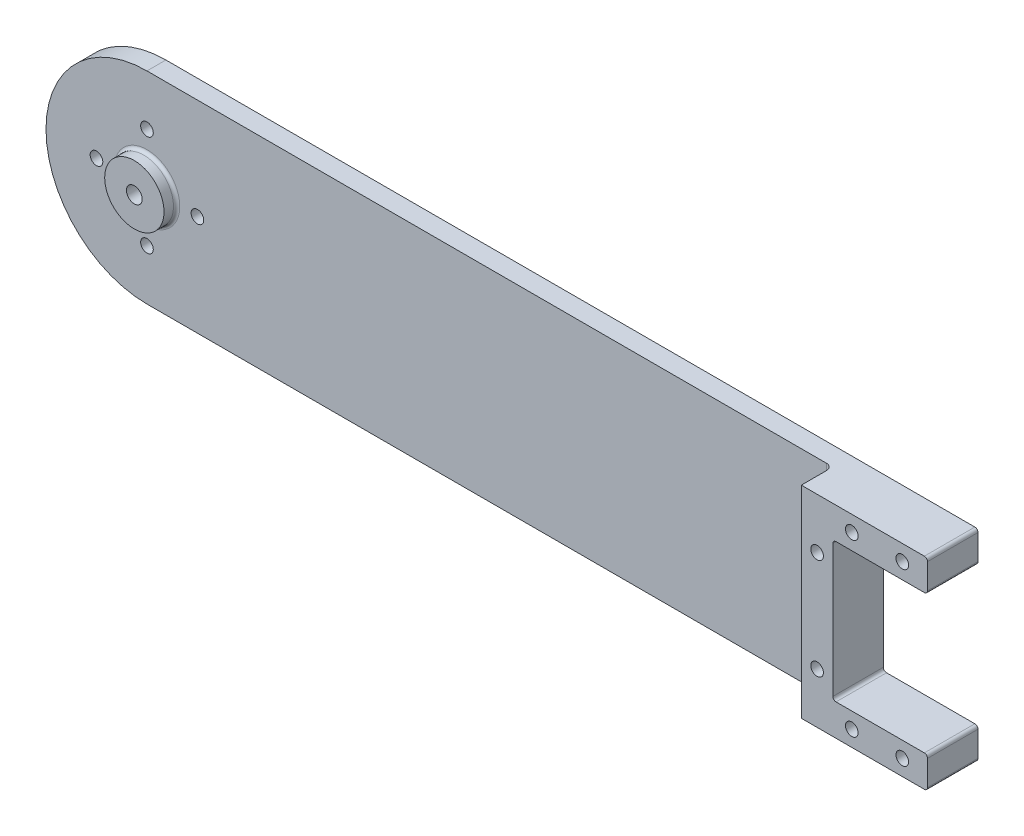
SolidWorks part; units mm, degrees
material "ABS"
ref_plane "Ön Düzlem" through (0, 0, 0) normal (0, 0, 1) x (1, 0, 0)
ref_plane "Üst Düzlem" through (0, 0, 0) normal (0, 1, 0) x (1, 0, 0)
ref_plane "Sağ Düzlem" through (0, 0, 0) normal (1, 0, 0) x (0, 0, -1)
sketch "Çizim1" plane through (0, 0, 0) normal (0, 0, 1) x (1, 0, 0)
  line L0 (-61, -16) -> (59, -16)
  line L1 (-61, 16) -> (59, 16)
  line L3 (59, 16) -> (75, 16)
  line L4 (59, 16) -> (59, -16)
  line L5 (59, -16) -> (75, -16)
  line L6 (75, 16) -> (75, -16)
  arc A0 (59, 16) -> (75, 0) centre (59, 0) cw
  arc A1 (-61, 16) -> (-77, 0) centre (-61, 0) ccw
  circle A2 centre (-61, 0) radius 16
  circle A3 centre (59, 0) radius 16
  point P0 (0, 0)
  dimension "D3" = 16
  dimension "D4" = 32
  dimension "D5" = 32
  dimension "D7" = 16
  dimension "D8" = 61
  dimension "D2" = 120
  dimension "D6" = 120
  dimension "D9" = 16
  dimension "D10" = 32
  dimension "D11" = 16
  dimension "D12" = 152
extrude "Yükseklik-Ekstrüzyon1" add sketch "Çizim1" along normal blind 3 contours A3 L1 A2 L0 | A0 A3 | A3 | L4 L3 L6 L5 | A2 region at (-1, 0, 0) region at (65.7906, 0, 0)
sketch "Çizim2" plane through (0, 0, 3) normal (0, 0, 1) x (1, 0, 0)
  circle A0 centre (-61, 0) radius 8 construction
  circle A1 centre (-61, 0) radius 4
  point P4 (-61, 8)
  point P5 (-53, 0)
  point P6 (-61, -8)
  point P7 (-69, 0)
  dimension "D1" = 16
  dimension "D2" = 8
extrude "Kes-Ekstrüzyon1" cut sketch "Çizim2" against normal blind 0.6
sketch "Çizim3" plane through (0, 0, 2.4) normal (0, 0, 1) x (1, 0, 0)
  circle A0 centre (-61, 0) radius 2.15
  dimension "D1" = 4.3
extrude "Kes-Ekstrüzyon3" cut sketch "Çizim3" against normal through all
hole_wizard "M2 Düz Başlı Makine Vidası İçin Havşa1" positions "3B Çizim1" profile "Çizim7" countersink size "M2" standard "ANSI Metrik" end condition through all
sketch3d "3B Çizim1"
  point P0 (-61, 8, 3)
  point P3 (-53, 0, 3)
  point P6 (-61, -8, 3)
  point P9 (-69, 0, 3)
sketch "Çizim7" plane through (-61, 8, 3) normal (1, 0, 0) x (0, -1, 0)
  line L0 (0, 0) -> (0, 6)
  line L1 (0, 6) -> (1, 6)
  line L2 (1, 6) -> (1, 0.3)
  line L3 (1, 0.3) -> (1.3, 0)
  line L5 (1.3, 0) -> (0, 0)
  line L6 (-1, 0.3) -> (-1.3, 0) construction
  line L11 (0, -6.35) -> (0, 107.95) construction
  dimension "Thru Hole Dia." = 2
  dimension "Thru Hole Depth" = 6
  dimension "Near C'Sink Dia." = 2.6
  dimension "Near C'Sink Angle" = 90
thread "Diş2" pitch 0.4 method cut profile "Diş Profili3" start angle 0, offset 0, length 5, pitch 0.4, diameter 2
ref_plane "Düzlem3" through (-62, 8, 2.7) normal (0, -1, 0) x (-1, 0, 0)
sketch "Diş Profili3" plane through (-62, 8, 2.7) normal (0, -1, 0) x (-1, 0, 0)
  line L0 (0, 0) -> (0, 0.4) construction
  line L1 (0, 0) -> (0.2165, 0.125)
  line L2 (0.2165, 0.125) -> (0.2165, 0.175)
  line L3 (0.2165, 0.175) -> (0, 0.3)
  line L4 (0.2165, 0.15) -> (0, 0.15) construction
  line L11 (0, 0) -> (0, 0.3)
  point P2 (0, 0)
  dimension "Pitch" = 0.4
  dimension "Profile_Angle" = 60
  dimension "Profile_Land" = 0.05
  dimension "Profile_Height" = 0.2165
pattern_circular "Dairesel Kaplama1" count 4 over 360 about axis through (-61, 0, 3) along (0, 0, 1) of "Diş2"
sketch "Çizim26" plane through (0, 0, 3) normal (0, 0, 1) x (1, 0, 0)
  line L0 (75, 16) -> (75, -16) construction
  line L1 (75, 11) -> (52.7, 11)
  line L2 (75, 11) -> (75, -11)
  line L3 (75, -11) -> (52.7, -11)
  line L4 (52.7, 11) -> (52.7, -11)
  line L5 (-61, -16) -> (75, -16) construction
  line L6 (-61, 16) -> (75, 16) construction
  point P8 (71.7, 13.5)
  point P9 (63.7, 13.5)
  point P10 (55.7, 13.5)
  point P11 (50.2, 8)
  point P12 (50.2, -8)
  point P13 (55.7, -13.5)
  point P14 (63.7, -13.5)
  point P15 (71.7, -13.5)
  dimension "D1" = 22.3
  dimension "D2" = 22
  dimension "D3" = 5
  dimension "D4" = 8
  dimension "D5" = 8
  dimension "D6" = 8
  dimension "D7" = 8
  dimension "D8" = 2.5
  dimension "D9" = 2.5
  dimension "D10" = 3.3
  dimension "D11" = 3.3
  dimension "D12" = 8
  dimension "D13" = 2.5
  dimension "D14" = 2.5
  dimension "D15" = 8
extrude "Kes-Ekstrüzyon4" cut sketch "Çizim26" against normal through all
sketch "Vida Del. Ref" plane through (0, 0, 0) normal (0, 0, -1) x (-1, 0, 0)
  point P0 (-71.7, 13.5)
  point P1 (-63.7, 13.5)
  point P3 (-55.7, 13.5)
  point P5 (-50.2, 8)
  point P7 (-50.2, -8)
  point P9 (-55.7, -13.5)
  point P11 (-63.7, -13.5)
  point P13 (-71.7, -13.5)
hole_wizard "M2 Düz Başlı Makine Vidası İçin Havşa2" positions "3B Çizim4" profile "Çizim32" countersink size "M2" standard "ANSI Metrik" end condition through all
sketch3d "3B Çizim4"
  point P0 (71.7, 13.5, 0)
  point P3 (63.7, 13.5, 0)
  point P6 (55.7, 13.5, 0)
  point P9 (50.2, 8, 0)
  point P12 (50.2, -8, 0)
  point P15 (55.7, -13.5, 0)
  point P18 (63.7, -13.5, 0)
  point P21 (71.7, -13.5, 0)
sketch "Çizim32" plane through (71.7, 13.5, 0) normal (1, 0, 0) x (0, 1, 0)
  line L0 (0, 0) -> (0, 3)
  line L1 (0, 3) -> (1.1, 3)
  line L2 (1.1, 3) -> (1.1, 0.2)
  line L3 (1.1, 0.2) -> (1.3, 0)
  line L5 (1.3, 0) -> (0, 0)
  line L6 (-1.1, 0.2) -> (-1.3, 0) construction
  line L11 (0, -6.35) -> (0, 107.95) construction
  dimension "Thru Hole Dia." = 2.2
  dimension "Thru Hole Depth" = 3
  dimension "Near C'Sink Dia." = 2.6
  dimension "Near C'Sink Angle" = 90
mirror "Sol Link Başlangıç" about plane through (0, 0, 0) normal (0, 0, 1) of "Kes-Ekstrüzyon4", "Kes-Ekstrüzyon3", "Kes-Ekstrüzyon1", "Yükseklik-Ekstrüzyon1", "M2 Düz Başlı Makine Vidası İçin Havşa1"
sketch "Çizim35" plane through (0, 16, 0) normal (0, 1, 0) x (1, 0, 0)
  line L0 (75, -3) -> (75, 3) construction
  line L1 (-77, -3) -> (75, -3)
  line L2 (-77, -3) -> (-77, 0)
  line L3 (-77, 0) -> (75, 0)
  line L4 (75, -3) -> (75, 0)
extrude "Kes-Ekstrüzyon5" cut sketch "Çizim35" against normal through all
sketch "Çizim37" plane through (0, 0, 0) normal (0, 0, 1) x (1, 0, 0)
  circle A0 centre (-61, 0) radius 3.75
  circle A1 centre (-61, 0) radius 2.15
  dimension "D1" = 4.3
  dimension "D2" = 7.5
extrude "Yükseklik-Ekstrüzyon2" add sketch "Çizim37" along normal blind 2
sketch "Çizim38" plane through (0, 0, -3) normal (0, 0, -1) x (-1, 0, 0)
  line L0 (61, -16) -> (-75, -16) construction
  line L1 (-75, 16) -> (-47.7, 16)
  line L2 (-75, 16) -> (-75, -16)
  line L3 (-75, -16) -> (-47.7, -16)
  line L4 (-47.7, 16) -> (-47.7, -16)
  line L6 (-75, 11) -> (-52.7, 11)
  line L7 (-75, 11) -> (-75, -11)
  line L8 (-75, -11) -> (-52.7, -11)
  line L9 (-52.7, 11) -> (-52.7, -11)
  line M8 (-75, 16) -> (-75, 11)
  line M9 (-75, 11) -> (-52.7, 11)
  line M10 (-52.7, 11) -> (-52.7, -11)
  line M11 (-52.7, -11) -> (-75, -11)
  line M12 (-75, -11) -> (-75, -16)
  line M13 (-75, -16) -> (61, -16)
  line M15 (61, 16) -> (-75, 16)
  dimension "D1" = 5
extrude "Yükseklik-Ekstrüzyon3" add sketch "Çizim38" against normal blind 8 contours L4 M15 M8 M9 M10 M11 M12 M13 region at (61.35, 15.5794, -3)
sketch "Vida Del. Ref_v2" plane through (0, 0, -3) normal (0, 0, -1) x (-1, 0, 0)
  point P0 (-71.7, 13.5)
  point P1 (-63.7, 13.5)
  point P3 (-55.7, 13.5)
  point P5 (-50.2, 8)
  point P7 (-50.2, -8)
  point P9 (-55.7, -13.5)
  point P11 (-63.7, -13.5)
  point P13 (-71.7, -13.5)
hole_wizard "M2 Düz Başlı Makine Vidası İçin Havşa3" positions "3B Çizim5" profile "Çizim40" countersink size "M2" standard "ANSI Metrik" end condition through all
sketch3d "3B Çizim5"
  point P0 (71.7, 13.5, -3)
  point P3 (63.7, 13.5, -3)
  point P6 (55.7, 13.5, -3)
  point P9 (50.2, 8, -3)
  point P12 (50.2, -8, -3)
  point P15 (55.7, -13.5, -3)
  point P18 (63.7, -13.5, -3)
  point P21 (71.7, -13.5, -3)
sketch "Çizim40" plane through (71.7, 13.5, -3) normal (1, 0, 0) x (0, 1, 0)
  line L0 (0, 0) -> (0, 8)
  line L1 (0, 8) -> (1, 8)
  line L2 (1, 8) -> (1, 0.3)
  line L3 (1, 0.3) -> (1.3, 0)
  line L5 (1.3, 0) -> (0, 0)
  line L6 (-1, 0.3) -> (-1.3, 0) construction
  line L11 (0, -6.35) -> (0, 107.95) construction
  dimension "Thru Hole Dia." = 2
  dimension "Thru Hole Depth" = 8
  dimension "Near C'Sink Dia." = 2.6
  dimension "Near C'Sink Angle" = 90
fillet "Radyus1" radius 1 1 edges at (47.7, 0, 0)
sketch "Çizim42" plane through (0, 0, -3) normal (0, 0, -1) x (-1, 0, 0)
  line L0 (61, -16) -> (-75, -16) construction
  line L1 (-75, 16) -> (-67.7, 16)
  line L2 (-75, 16) -> (-75, -16)
  line L3 (-75, -16) -> (-67.7, -16)
  line L4 (-67.7, 16) -> (-67.7, -16)
  dimension "D1" = 7.3
extrude "Kes-Ekstrüzyon6" cut sketch "Çizim42" against normal through all
sketch "Çizim43" plane through (0, 0, 0) normal (0, 0, 1) x (1, 0, 0)
  circle A0 centre (-61, 0) radius 4.7
  circle A1 centre (-61, 0) radius 2.15
  dimension "D1" = 4.3
  dimension "D2" = 9.4
extrude "Yükseklik-Ekstrüzyon4" add sketch "Çizim43" along normal blind 2
sketch "Çizim44" plane through (0, 0, 2) normal (0, 0, 1) x (1, 0, 0)
  circle A0 centre (-61, 0) radius 2.15
extrude "Yükseklik-Ekstrüzyon5" add sketch "Çizim44" against normal blind 3
sketch "Çizim46" plane through (0, 0, -2.4) normal (0, 0, -1) x (-1, 0, 0)
  circle A0 centre (61, 0) radius 2.15
  circle A1 centre (61, 0) radius 4
  dimension "D1" = 4.3
  dimension "D2" = 8
extrude "Yükseklik-Ekstrüzyon6" add sketch "Çizim46" along normal blind 0.6
hole_wizard "M3 Düz Başlı Makine Vidası İçin Havşa1" positions "3B Çizim6" profile "Çizim47" countersink size "M3" standard "ANSI Metrik"
sketch3d "3B Çizim6"
  line L0 (-61, 0, -3) -> (-61, 0, -1) construction
  point P0 (-61, 0, -1)
sketch "Çizim47" plane through (-61, 0, -1) normal (1, 0, 0) x (0, 1, 0)
  line L0 (0, 0) -> (0, 3)
  line L1 (0, 3) -> (1.25, 3)
  line L2 (1.25, 3) -> (1.25, 0.3)
  line L3 (1.25, 0.3) -> (1.55, 0)
  line L5 (1.55, 0) -> (0, 0)
  line L6 (-1.25, 0.3) -> (-1.55, 0) construction
  line L10 (0, 3) -> (-1.25, 3) construction
  line L11 (0, -6.35) -> (0, 107.95) construction
  dimension "Hole Dia." = 2.5
  dimension "Hole Depth" = 3
  dimension "Near C'Sink Dia." = 3.1
  dimension "Near C'Sink Angle" = 90
  dimension "Drill Angle" = 180
fillet "Radyus2" radius 0.5 7 edges at (52.7, -11, 1) (52.7, 11, 1) (67.7, -16, 1) (67.7, -11, 1) (67.7, 11, 1) (67.7, 16, 1) (-65.7, 0, 0)
